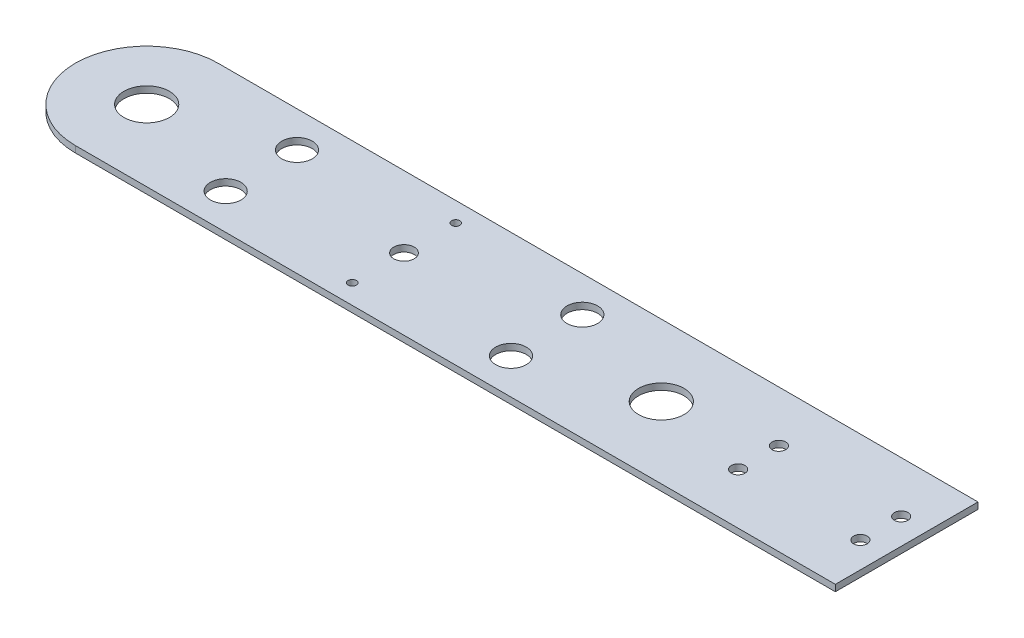
SolidWorks part; units mm, degrees
ref_plane "Front Plane" through (0, 0, 0) normal (0, 0, 1) x (1, 0, 0)
ref_plane "Top Plane" through (0, 0, 0) normal (0, 1, 0) x (1, 0, 0)
ref_plane "Right Plane" through (0, 0, 0) normal (1, 0, 0) x (0, 0, -1)
sketch "Sketch1" plane through (0, 0, 0) normal (0, 1, 0) x (1, 0, 0)
  line L0 (126.2582, 0) -> (-126.2582, 0)
  line L1 (-126.2582, 35) -> (126.2582, 35)
  line L3 (-126.2582, -35) -> (126.2582, -35)
  line L4 (-70, 35) -> (-70, 0) construction
  line L5 (-70, 0) -> (-70, -35) construction
  line L6 (70, 35) -> (70, 0) construction
  line L7 (70, 0) -> (70, -35) construction
  line L8 (0, -35) -> (0, 35) construction
  line L9 (161.2582, -35) -> (161.2582, 35) construction
  line L10 (161.2582, -35) -> (126.2582, -35)
  line L11 (161.2582, 35) -> (126.2582, 35)
  line L12 (246.6582, 0) -> (161.2582, 0) construction
  line L13 (161.2582, -35) -> (246.6582, -35)
  line L15 (161.2582, 35) -> (246.6582, 35)
  line L16 (246.6582, -35) -> (246.6582, 35)
  line L17 (203.9582, 10) -> (203.9582, -10) construction
  line L18 (161.2582, 10) -> (246.6582, 10) construction
  line L19 (161.2582, -10) -> (246.6582, -10) construction
  circle A0 centre (-126.2582, 0) radius 35
  circle A2 centre (-126.2582, 0) radius 11.15
  circle A3 centre (126.2582, 0) radius 11.15
  circle A5 centre (-70, -17.5) radius 7.5
  circle A6 centre (-70, 17.5) radius 7.5
  circle A7 centre (70, 17.5) radius 7.5
  circle A8 centre (70, -17.5) radius 7.5
  circle A9 centre (0, 0) radius 5
  circle A10 centre (0, -25.4) radius 2.02
  circle A11 centre (0, 25.4) radius 2.02
  circle A14 centre (233.9582, -10) radius 3.325
  circle A15 centre (173.9582, -10) radius 3.325
  circle A16 centre (173.9582, 10) radius 3.325
  circle A17 centre (233.9582, 10) radius 3.325
  point P4 (0, 0)
  point P38 (161.2582, 0)
  point P39 (-161.2582, 0)
  point P45 (203.9582, 0)
  point P48 (203.9582, 10)
  point P53 (203.9582, -10)
  dimension "D1" = 22.3
  dimension "D2" = 10
  dimension "D3" = 70
  dimension "D4" = 15
  dimension "D7" = 25.4
  dimension "D8" = 25.4
  dimension "D9" = 4.04
  dimension "D10" = 4.04
  dimension "D13" = 6.65
  dimension "D5" = 70
  dimension "D6" = 70
  dimension "D11" = 20
  dimension "D12" = 322.5164
  dimension "D14" = 60
  dimension "D15" = 60
  dimension "D16" = 12.7
  dimension "D17" = 12.7
  dimension "D18" = 12.7
extrude "Boss-Extrude1" add sketch "Sketch1" along normal blind 3.175 contours A9 A3 A0 L3 L10 L13 L16 L15 L11 L1 A11 A10 A8 A7 A6 A5 | A2 A0 region at (-102.2095, 0, 24.0487) region at (-98.8265, 0, -27.4317)
